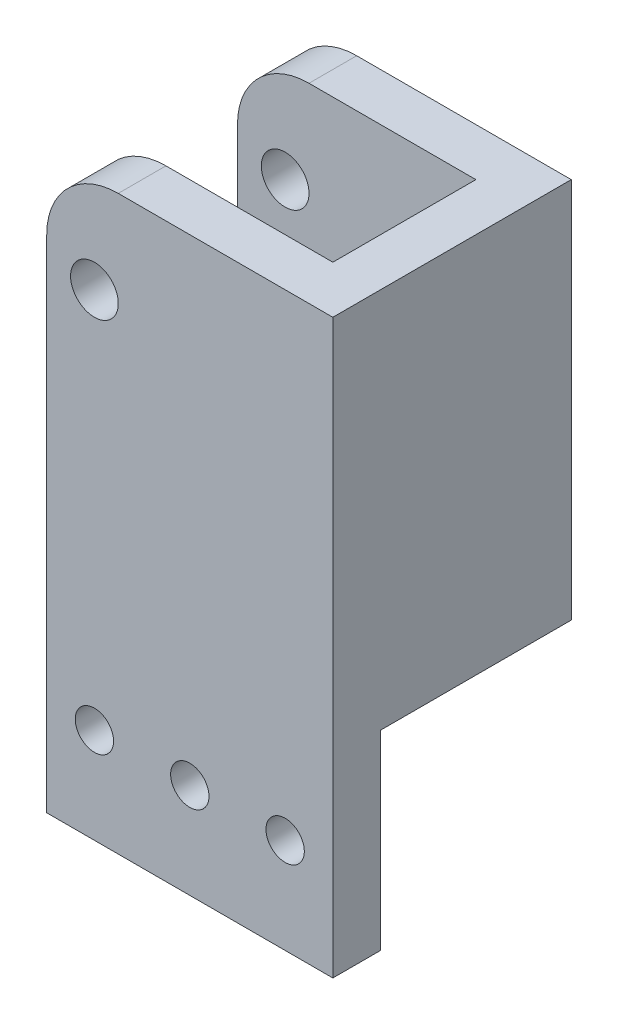
SolidWorks part; units mm, degrees
ref_plane "Front Plane" through (0, 0, 0) normal (0, 0, 1) x (1, 0, 0)
ref_plane "Top Plane" through (0, 0, 0) normal (0, 1, 0) x (1, 0, 0)
ref_plane "Right Plane" through (0, 0, 0) normal (1, 0, 0) x (0, 0, -1)
sketch "Sketch1" plane through (0, 0, 0) normal (0, 0, 1) x (1, 0, 0)
  line L1 (0, 0) -> (38.1, 0)
  line L2 (0, 0) -> (0, 76.2)
  line L3 (0, 76.2) -> (38.1, 76.2)
  line L4 (38.1, 0) -> (38.1, 76.2)
  dimension "D1" = 76.2
  dimension "D2" = 38.1
extrude "Boss-Extrude1" add sketch "Sketch1" against normal blind 31.75
sketch "Sketch2" plane through (0, 76.2, 0) normal (0, 1, 0) x (1, 0, 0)
  line L0 (0, 0) -> (0, 6.35)
  line L1 (0, 31.75) -> (0, 0) construction
  line L2 (0, 6.35) -> (31.75, 6.35)
  line L3 (31.75, 6.35) -> (31.75, 31.75)
  line L4 (38.1, 31.75) -> (0, 31.75) construction
  line L5 (38.1, 31.75) -> (38.1, 0) construction
  line L6 (31.75, 6.35) -> (31.75, 25.4) construction
  dimension "D1" = 6.35
  dimension "D2" = 6.35
  dimension "D3" = 19.05
sketch "Sketch3" plane through (0, 0, 0) normal (-1, 0, 0) x (0, 0, 1)
  line L0 (-31.75, 0) -> (-6.35, 0)
  line L1 (-31.75, 0) -> (0, 0) construction
  line L4 (-31.75, 0) -> (-31.75, 76.2)
  line L5 (-31.75, 76.2) -> (-6.35, 76.2)
  line L6 (-6.35, 0) -> (-6.35, 76.2)
  dimension "D1" = 25.4
  dimension "D2" = 76.2
extrude "Cut-Extrude2" cut sketch "Sketch3" against normal blind 31.75
sketch "Sketch4" plane through (31.75, 0, 0) normal (-1, 0, 0) x (0, 0, 1)
  line L0 (-6.35, 0) -> (-6.35, 76.2) construction
  line L1 (-31.75, 0) -> (-6.35, 0)
  line L2 (-31.75, 0) -> (-31.75, 25.4)
  line L3 (-31.75, 25.4) -> (-6.35, 25.4)
  line L4 (-6.35, 0) -> (-6.35, 25.4)
  dimension "D1" = 25.4
extrude "Cut-Extrude3" cut sketch "Sketch4" against normal through all
sketch "Sketch5" plane through (0, 76.2, 0) normal (0, 1, 0) x (1, 0, 0)
  line L0 (38.1, 31.75) -> (38.1, 0) construction
  line L1 (38.1, 0) -> (0, 0) construction
  line L2 (0, 0) -> (0, 6.35) construction
  line L3 (0, 6.35) -> (31.75, 6.35) construction
  line L4 (31.75, 6.35) -> (31.75, 31.75) construction
  line L5 (31.75, 31.75) -> (38.1, 31.75) construction
  line L6 (31.75, 6.35) -> (31.75, 25.4)
  line L7 (31.75, 31.75) -> (0, 31.75)
  line L8 (0, 31.75) -> (0, 25.4)
  line L9 (0, 25.4) -> (31.75, 25.4)
  line M6 (31.75, 31.75) -> (31.75, 6.35)
  dimension "D1" = 19.05
extrude "Boss-Extrude2" add sketch "Sketch5" against normal blind 50.8 contours L8 L9 L7 M6 region at (15.875, 76.2, -28.575)
sketch "Sketch6" plane through (0, 0, -31.75) normal (0, 0, -1) x (-1, 0, 0)
  line L0 (0, 76.2) -> (0, 63.5) construction
  line L1 (0, 25.4) -> (0, 76.2) construction
  line L2 (0, 63.5) -> (-6.35, 63.5) construction
  circle A0 centre (-6.35, 63.5) radius 3.175
  dimension "D3" = 6.35
  dimension "D1" = 12.7
  dimension "D2" = 6.35
extrude "Cut-Extrude4" cut sketch "Sketch6" against normal blind 50.8
fillet "Fillet2" radius 9.525 2 edges at (0, 76.2, -3.175) (0, 76.2, -28.575)
ref_plane "Plane1" through (0, 25.4, 0) normal (0, -1, 0) x (-1, 0, 0)
sketch "Sketch7" plane through (0, 25.4, 0) normal (0, -1, 0) x (-1, 0, 0)
  line L1 (0, 25.4) -> (-31.75, 25.4)
  line L2 (0, 25.4) -> (0, 6.35)
  line L3 (0, 6.35) -> (-31.75, 6.35)
  line L4 (-31.75, 25.4) -> (-31.75, 6.35)
extrude "Boss-Extrude3" add sketch "Sketch7" against normal blind 6.35
sketch "Sketch8" plane through (0, 0, 0) normal (0, 0, 1) x (1, 0, 0)
  line L0 (38.1, 0) -> (38.1, 76.2) construction
  line L1 (0, 0) -> (38.1, 0)
  line L2 (0, 0) -> (0, 25.4)
  line L3 (0, 25.4) -> (38.1, 25.4)
  line L4 (38.1, 0) -> (38.1, 25.4)
  line L5 (0, 12.7) -> (38.1, 12.7) construction
  line L6 (6.35, 25.4) -> (6.35, 0) construction
  line L7 (19.05, 25.4) -> (19.05, 0) construction
  line L8 (31.75, 25.4) -> (31.75, 0) construction
  circle A0 centre (6.35, 12.7) radius 6.35
  circle A1 centre (19.05, 12.7) radius 6.35
  circle A2 centre (31.75, 12.7) radius 6.35
  dimension "D4" = 12.7
  dimension "D5" = 12.7
  dimension "D6" = 12.7
  dimension "D1" = 25.4
  dimension "D2" = 6.35
  dimension "D3" = 6.35
hole_wizard "1/4-20 Tapped Hole1" positions "3DSketch1" profile "Sketch9" tap size "1/4-20" standard "ANSI Inch"
sketch3d "3DSketch1"
  point P0 (6.35, 12.7, 0)
  point P3 (19.05, 12.7, 0)
  point P6 (31.75, 12.7, 0)
sketch "Sketch9" plane through (6.35, 12.7, 0) normal (1, 0, 0) x (0, -1, 0)
  line L0 (0, 0) -> (0, 20.5838)
  line L1 (0, 20.5838) -> (2.5527, 19.05)
  line L2 (2.5527, 19.05) -> (2.5527, 0)
  line L5 (2.5527, 0) -> (0, 0)
  line L10 (0, 20.5838) -> (-2.5527, 19.05) construction
  line L11 (0, -6.35) -> (0, 107.95) construction
  dimension "Tap Drill Dia." = 5.1054
  dimension "Tap Drill Depth" = 19.05
  dimension "Drill Angle" = 118
cosmetic thread "Hole Thread1" parameters "D1"=6.35, "D2"=6.35
cosmetic thread "Hole Thread2" parameters "D1"=6.35, "D2"=6.35
cosmetic thread "Hole Thread3" parameters "D1"=6.35, "D2"=6.35
